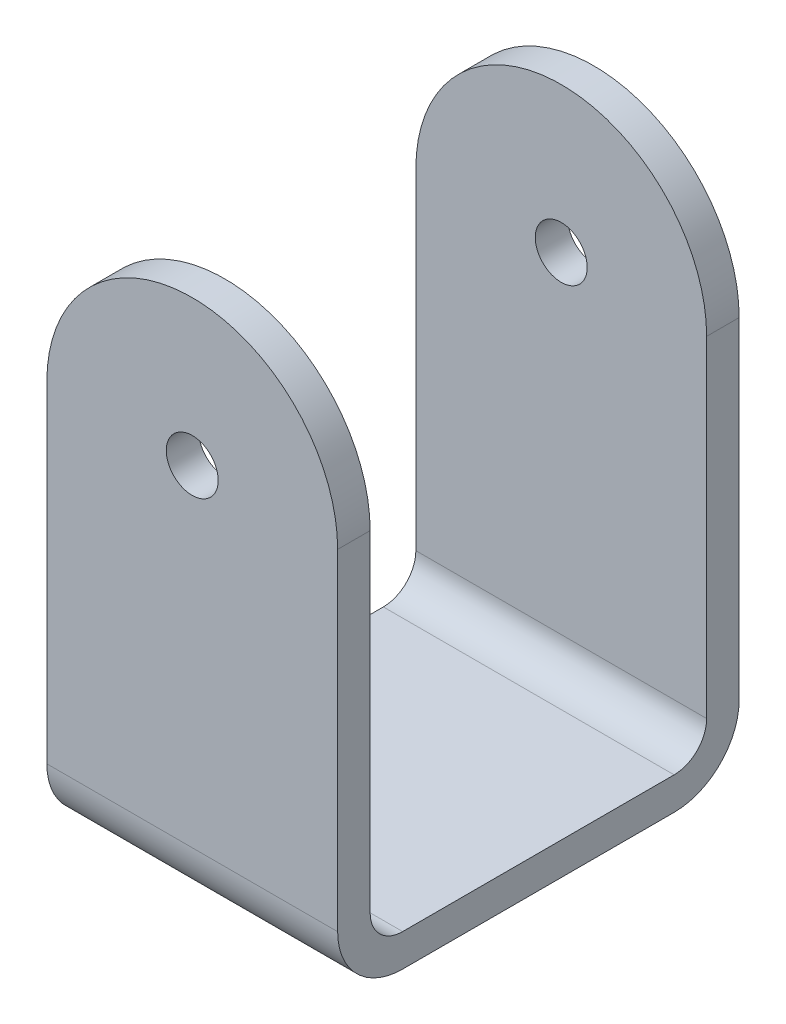
SolidWorks part; units mm, degrees
ref_plane "Front Plane" through (0, 0, 0) normal (0, 0, 1) x (1, 0, 0)
ref_plane "Top Plane" through (0, 0, 0) normal (0, 1, 0) x (1, 0, 0)
ref_plane "Right Plane" through (0, 0, 0) normal (1, 0, 0) x (0, 0, -1)
sketch "Sketch1" plane through (0, 0, 0) normal (1, 0, 0) x (0, 0, -1)
  line L0 (33.2247, 0) -> (-33.2247, 0)
  line L1 (-49.0997, 15.875) -> (-49.0997, 132.4102)
  line L2 (-49.0997, 132.4102) -> (-41.1495, 132.4102)
  line L3 (-41.1495, 132.4102) -> (-41.1495, 15.9004)
  line L4 (-33.1993, 7.9502) -> (33.1993, 7.9502)
  line L6 (0, 18.6744) -> (0, -19.7958) construction
  line L7 (41.1495, 132.4102) -> (41.1495, 15.9004)
  line L8 (49.0997, 132.4102) -> (41.1495, 132.4102)
  line L9 (49.0997, 15.875) -> (49.0997, 132.4102)
  arc A0 (-41.1495, 15.9004) -> (-33.1993, 7.9502) centre (-33.1993, 15.9004) ccw
  arc A1 (-33.2247, 0) -> (-49.0997, 15.875) centre (-33.2247, 15.875) cw
  arc A2 (41.1495, 15.9004) -> (33.1993, 7.9502) centre (33.1993, 15.9004) cw
  arc A3 (33.2247, 0) -> (49.0997, 15.875) centre (33.2247, 15.875) ccw
  point P0 (44.45, 4.6497)
  point P7 (-44.45, 4.6497)
  point P9 (-45.1246, 132.4102)
  dimension "D1" = 132.4102
  dimension "D2" = 7.9502
  dimension "D3" = 15.875
  dimension "D4" = 88.9
  dimension "D5" = 7.9502
  dimension "D6" = 7.9502
extrude "Boss-Extrude2" add sketch "Sketch1" along normal blind 71.12
sketch "Sketch6" plane through (0, 0, 49.0997) normal (0, 0, 1) x (1, 0, 0)
  line L0 (71.12, 132.4102) -> (0, 132.4102) construction
  line L1 (71.12, 0) -> (0, 0) construction
  line L4 (0, 132.4102) -> (0, 15.875) construction
  line L5 (71.12, 132.4102) -> (71.12, 15.875) construction
  circle A0 centre (35.56, 96.8502) radius 6.35
  arc A1 (0, 96.8502) -> (71.12, 96.8502) centre (35.56, 96.8502) cw
  line M2 (0, 132.4102) -> (0, 15.875)
  line M4 (71.12, 15.875) -> (71.12, 132.4102)
  line M5 (71.12, 132.4102) -> (0, 132.4102)
  dimension "D1" = 132.4102
extrude "Cut-Extrude1" cut sketch "Sketch6" against normal through all contours A1 M5 M4 | A1 M2 M5 region at (7.943, 124.4672, 49.0997) region at (63.177, 124.4672, 49.0997)
extrude "Cut-Extrude2" cut sketch "Sketch6<3>" against normal through all contours A0
sketch "Sketch6<3>" plane through (0, 0, 49.0997) normal (0, 0, 1) x (1, 0, 0) same geometry as "Sketch6"
